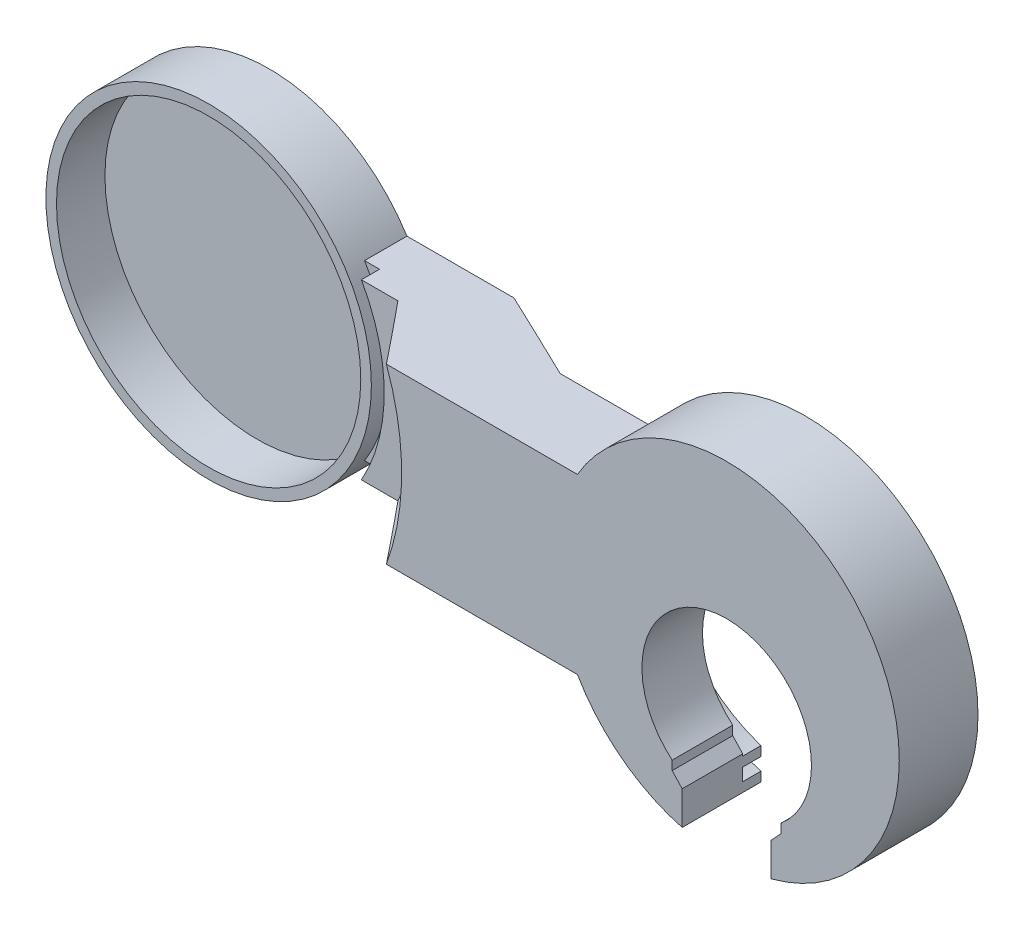
SolidWorks part; units mm, degrees
material "Custom Plastic"
ref_plane "Front Plane" through (0, 0, 0) normal (0, 0, 1) x (1, 0, 0)
ref_plane "Top Plane" through (0, 0, 0) normal (0, 1, 0) x (1, 0, 0)
ref_plane "Right Plane" through (0, 0, 0) normal (1, 0, 0) x (0, 0, -1)
sketch "Sketch1" plane through (0, 0, 0) normal (0, 0, 1) x (1, 0, 0)
  circle A0 centre (0, 0) radius 26.875
  dimension "D1" = 53.75
extrude "Boss-Extrude1" add sketch "Sketch1" along normal blind 2
sketch "Sketch2" plane through (0, 0, 2) normal (0, 0, 1) x (1, 0, 0)
  circle A0 centre (0, 0) radius 26.875
  circle A1 centre (0, 0) radius 25.125
  dimension "D1" = 50.25
  dimension "D2" = 53.75
extrude "Boss-Extrude2" add sketch "Sketch2" along normal blind 8
ref_plane "Plane1" through (0, 0, 20) normal (0, 0, 1) x (1, 0, 0)
sketch "Sketch3" plane through (0, 0, 20) normal (0, 0, 1) x (1, 0, 0)
  line L0 (70.9021, 14.31) -> (22.7484, 14.31)
  line L5 (70.9021, -14.31) -> (22.7484, -14.31)
  arc A2 (70.9021, -14.31) -> (70.9021, 14.31) centre (95.5491, 0) ccw
  circle A3 centre (0, 0) radius 26.875 construction
  arc A4 (22.7484, 14.31) -> (22.7484, -14.31) centre (0, 0) cw
  dimension "D2" = 57
extrude "Boss-Extrude3" add sketch "Sketch3" against normal blind 13 contours A2 L0 A4 L5
chamfer "Chamfer1" distance 20 distance2 15 1 edges at (26.875, 0, 20) first distance on face at (24.8117, 0, 15)
sketch "Sketch4" plane through (0, 0, 7) normal (0, 0, -1) x (-1, 0, 0)
  circle A0 centre (-95.5491, 0) radius 23.5
  circle A1 centre (-95.5491, 0) radius 27
  circle A2 centre (-95.5491, 0) radius 25
  dimension "D1" = 47
  dimension "D2" = 54
  dimension "D3" = 50
extrude "Cut-Extrude1" cut sketch "Sketch4" against normal blind 3 contours A0 | A1 A2 region at (95.5491, 0, 7) region at (121.7855, 0, 7)
sketch "Sketch5" plane through (0, 0, 10) normal (0, 0, -1) x (-1, 0, 0)
  line L0 (-95.5491, 0) -> (-95.5491, -8) construction
  line L5 (-104.5491, -18.7238) -> (-104.5491, -20.2238)
  line L6 (-104.5491, -20.2238) -> (-102.8991, -22)
  line L7 (-102.8991, -22) -> (-102.8991, -27.5359)
  line L9 (-88.1991, -27.5359) -> (-88.1991, -22)
  line L10 (-88.1991, -22) -> (-86.5491, -20.2238)
  line L11 (-86.5491, -20.2238) -> (-86.5491, -18.7238)
  arc A0 (-86.5491, -18.7238) -> (-81.9809, -11.45) centre (-95.5491, -8) ccw
  arc A2 (-81.9809, -4.55) -> (-109.1174, -4.55) centre (-95.5491, -8) ccw
  arc A4 (-109.1174, -11.45) -> (-104.5491, -18.7238) centre (-95.5491, -8) ccw
  arc A5 (-70.9021, 14.31) -> (-70.9021, -14.31) centre (-95.5491, 0) ccw construction
  arc A6 (-102.8991, -27.5359) -> (-88.1991, -27.5359) centre (-95.5491, 0) ccw
  arc A7 (-109.1174, -4.55) -> (-109.1174, -11.45) centre (-95.5491, -8) ccw
  arc A8 (-81.9809, -4.55) -> (-81.9809, -11.45) centre (-95.5491, -8) cw
  dimension "D1" = 8
extrude "Cut-Extrude2" cut sketch "Sketch5" against normal through all both and the other way through all
chamfer "Chamfer2" distance 30 distance2 15 1 edges at (26.875, 0, 7) first distance on face at (75.45, -3.9806, 7)
sketch "Sketch8" plane through (0, 0, 10) normal (0, 0, 1) x (1, 0, 0)
  circle A0 centre (0, 0) radius 25.125
  circle A1 centre (0, 0) radius 26.875
  circle A2 centre (0, 0) radius 29
  line M4 (22.7484, -14.31) -> (31.2548, -14.31)
  line M6 (31.2548, 14.31) -> (22.7484, 14.31)
  dimension "D1" = 53.75
  dimension "D2" = 50.25
  dimension "D3" = 58
extrude "Cut-Extrude4" cut sketch "Sketch8" against normal blind 3 contours A2 A1 M4 M6 region at (26.1042, 7.5277, 10)
